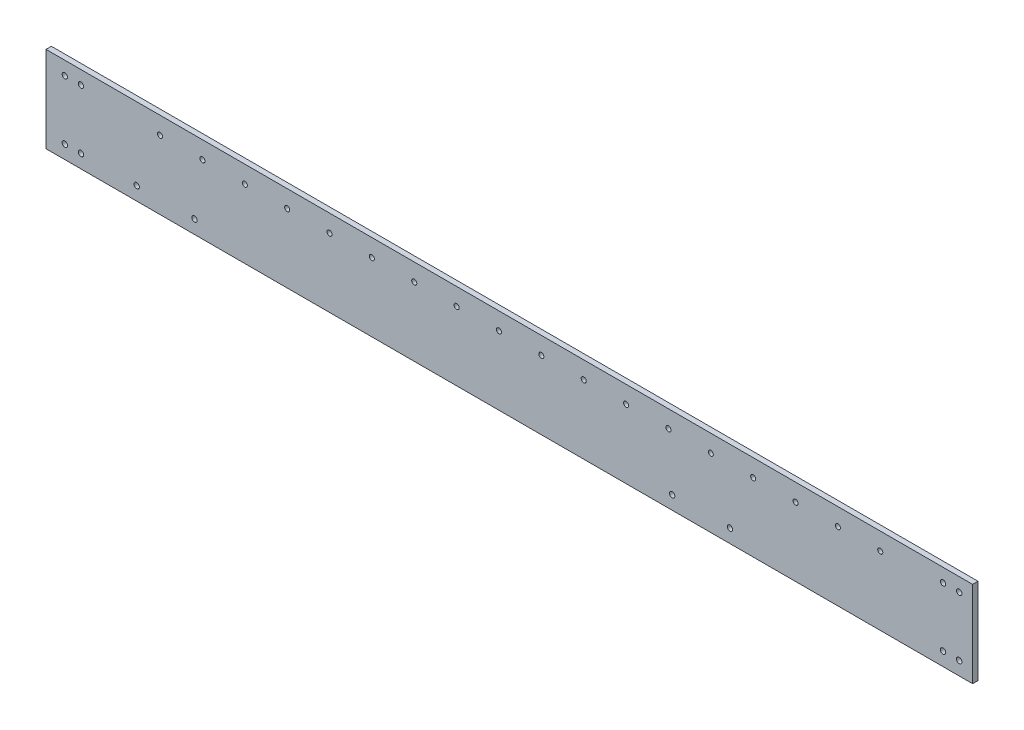
SolidWorks part; units mm, degrees
ref_plane "Front Plane" through (0, 0, 0) normal (0, 0, 1) x (1, 0, 0)
ref_plane "Top Plane" through (0, 0, 0) normal (0, 1, 0) x (1, 0, 0)
ref_plane "Right Plane" through (0, 0, 0) normal (1, 0, 0) x (0, 0, -1)
sketch "Sketch1" plane through (0, 0, 0) normal (1, 0, 0) x (0, 0, -1)
  line L0 (0, 0) -> (-3.175, 0)
  line L3 (-3.175, 0) -> (-3.175, 50.8)
  line L4 (-3.175, 50.8) -> (0, 50.8)
  line L5 (0, 50.8) -> (0, 0)
  dimension "LHeight" = 50.8
  dimension "LMaterialThickness" = 3.175
extrude "Boss-Extrude1" add sketch "Sketch1" along normal blind 546.825
sketch "LeftSideHoles-Sketch4" plane through (0, 0, 3.175) normal (0, 0, 1) x (1, 0, 0)
  line L0 (546.825, 50.8) -> (546.825, 0) construction
  line L1 (0, 50.8) -> (0, 0) construction
  line L2 (546.825, 50.8) -> (546.825, 0) construction
  line L3 (546.825, 50.8) -> (0, 50.8) construction
  line L4 (546.825, 0) -> (0, 0) construction
  line L5 (546.825, 50.8) -> (0, 50.8) construction
  line L6 (0, 50.8) -> (0, 0) construction
  circle A1 centre (11.1125, 42.8625) radius 1.5875
  circle A3 centre (529.3625, 42.8625) radius 1.5875
  circle A4 centre (20.6375, 42.8625) radius 1.5875
  circle A5 centre (538.8875, 42.8625) radius 1.5875
  circle A6 centre (11.1125, 7.9375) radius 1.5875
  circle A7 centre (20.6375, 7.9375) radius 1.5875
  circle A8 centre (529.3625, 7.9375) radius 1.5875
  circle A9 centre (538.8875, 7.9375) radius 1.5875
  circle A10 centre (492.325, 40.575) radius 1.5
  circle A11 centre (467.325, 40.575) radius 1.5
  circle A12 centre (442.325, 40.575) radius 1.5
  circle A13 centre (417.325, 40.575) radius 1.5
  circle A14 centre (392.325, 40.575) radius 1.5
  circle A15 centre (367.325, 40.575) radius 1.5
  circle A16 centre (342.325, 40.575) radius 1.5
  circle A17 centre (317.325, 40.575) radius 1.5
  circle A18 centre (292.325, 40.575) radius 1.5
  circle A19 centre (267.325, 40.575) radius 1.5
  circle A20 centre (242.325, 40.575) radius 1.5
  circle A21 centre (217.325, 40.575) radius 1.5
  circle A22 centre (192.325, 40.575) radius 1.5
  circle A23 centre (167.325, 40.575) radius 1.5
  circle A24 centre (142.325, 40.575) radius 1.5
  circle A25 centre (117.325, 40.575) radius 1.5
  circle A26 centre (92.325, 40.575) radius 1.5
  circle A27 centre (67.325, 40.575) radius 1.5
  circle A28 centre (53.5125, 7.9375) radius 1.5875
  circle A31 centre (369.5125, 7.9375) radius 1.5875
  circle A33 centre (87.6375, 7.9375) radius 1.5875
  circle A35 centre (403.6375, 7.9375) radius 1.5875
  dimension "D2" = 3.175
  dimension "D10" = 3
  dimension "D14" = 3.175
  dimension "D4" = 7.9375
  dimension "D1" = 11.1125
  dimension "D6" = 20.6375
  dimension "D3" = 7.9375
  dimension "D5" = 17.4625
  dimension "D7" = 7.9375
  dimension "D8" = 54.5
  dimension "D9" = 10.225
  dimension "D12" = 25
  dimension "D13" = 7.9375
  dimension "D15" = 53.5125
  dimension "D17" = 316
  dimension "D20" = 34.125
  dimension "D16" = 34.125
  dimension "D11" = 18
extrude "LeftSideHoles-Cut-Extrude3" cut sketch "LeftSideHoles-Sketch4" against normal through all
equation "\"RailThickness\"= .125in'Spec"
equation "\"SideRailHoleY1FromEdge\"= \"HoleOffsetFromEdge\""
equation "\"SideRailHoleX1FromSide\"= \"HoleOffsetFromSide\""
equation "\"MidSideRailLength\"= \"SideRailLength\" - \"RailThickness\"'Equals 546.825 => MidSideRail buts up against MidBackRail"
equation "\"VSWidth\"= 1.25in'Spec"
equation "\"HoleOffsetFromEdge\"= \"RailThickness\" * 2.5"
equation "\"HoleOffsetFromSide\"= \"RailThickness\" * 3.5"
equation "\"SideRailHoleX2FromSide\"= \"VSWidth\" - \"HoleOffsetFromEdge\" - \"RailThickness\"'Equals 20.6375"
equation "\"FasteningHoleDiameter\"= .125in"
equation "\"D2@LeftSideHoles-Sketch4\" = \"FasteningHoleDiameter\""
equation "\"LHeight@Sketch1\"=\"MidLeftOrRightSideRailHeight\""
equation "\"LMaterialThickness@Sketch1\"=\"RailThickness\""
equation "\"D1@Boss-Extrude1\"=\"MidSideRailLength\""
equation "\"D4@LeftSideHoles-Sketch4\" = \"SideRailHoleY1FromEdge\""
equation "\"D1@LeftSideHoles-Sketch4\"=\"SideRailHoleX1FromSide\""
equation "\"D6@LeftSideHoles-Sketch4\"=\"SideRailHoleX2FromSide\" "
equation "\"D3@LeftSideHoles-Sketch4\"=\"SideRailHoleX1FromSide\" - \"RailThickness\""
equation "\"D5@LeftSideHoles-Sketch4\"=\"SideRailHoleX2FromSide\" - \"RailThickness\""
equation "\"D7@LeftSideHoles-Sketch4\"=\"HoleOffsetFromEdge\""
equation "\"LinearRailXMountHole\"= \"StepperWidth\" + \"LinearRailFirstHoleOffsetFromEdge\""
equation "\"D8@LeftSideHoles-Sketch4\"=\"LinearRailXMountHole\""
equation "\"D9@LeftSideHoles-Sketch4\"=\"V6.3 GantryMiddleToToTopOfMidSideRail\""
equation "\"LinearRailHoleDistance\"= 25mm'Spec"
equation "\"D12@LeftSideHoles-Sketch4\"=\"LinearRailHoleDistance\""
equation "\"LinearRailFirstHoleOffsetFromEdge\"= 12.5mm'Spec"
equation "\"SideRailLength\"= 550mm"
equation "\"MidLeftOrRightSideRailHeight\"= 2.0in"
equation "\"StepperWidth\"= 42mm'Spec"
equation "\"StepperHolePadSize\"= \"StepperHoleDiameter\""
equation "\"MidRailRodStabilizerMountingHoleOffsetFromEdge\"= \"HoleOffsetFromEdge\""
equation "\"D13@LeftSideHoles-Sketch4\"=\"MidRailRodStabilizerMountingHoleOffsetFromEdge\""
equation "\"D14@LeftSideHoles-Sketch4\"=\"FasteningHoleDiameter\""
equation "\"DistanceFromBedFrontToFirstLeftStepperHole\"= \"LeadScrewNutPadSize\" + 10mm'Equals 34"
equation "\"BeltTensionerDepth\"= \"BeltTensionerBackWallThickness\" + \"BeltTensionerInnerDepth\"'Equals 23.4"
equation "\"20TGT2PulleyDiameter\"= 17.9mm'Spec"
equation "\"BeltTensionerSpaceBetweenPulleyAndWall\"= 1.5mm"
equation "\"BeltTensionerBackWallThickness\"= 4mm"
equation "\"BeltTensionerInnerDepth\"= \"20TGT2PulleyDiameter\" + \"BeltTensionerSpaceBetweenPulleyAndWall\""
equation "\"DistanceFromFrontSideToBedFront\"= \"RailThickness\" + \"BeltTensionerDepth\" + 10mm'Equals 36.575"
equation "\"DistanceFromFrontSideToFirstLeftStepperHole\"= \"DistanceFromFrontSideToBedFront\" + \"DistanceFromBedFrontToFirstLeftStepperHole\"'Equals 70.575"
equation "\"DistanceBetweenFrontToBackStepperHoles\"= \"BedLength\" - \"DistanceFromBedFrontToFirstLeftStepperHole\"'Equals 316"
equation "\"BedLength\"= \"BedInnerSquareLength\" + \"BedLWidth\" * 2 - \"BedOverlap\" * 2 + \"BedIncreasedByLength\"'Equals 350"
equation "\"BedOverlap\"= 20mm"
equation "\"BedThirdSize\"= 70mm"
equation "\"BedInnerSquareWidth\"= \"BedThirdSize\" * 3'Equals 210"
equation "\"BedLWidth\"= \"BedThirdSize\" + \"BedOverlap\"'Equals 90"
equation "\"BedIncreasedByLength\"= 0mm"
equation "\"LM8UUDiameter\"= 15mm"
equation "\"RodStabilizerDepth\"= \"LM8UUDiameter\" * 2"
equation "\"BedInnerSquareLength\"= \"BedInnerSquareWidth\""
equation "\"DistanceFromFrontSideToFirstLeftRodStabilizerMountingHole\"= \"DistanceFromFrontSideToFirstLeftStepperHole\" - \"DistanceFromStepperHoleToRodStabilizerMountingHole\"'Equals 53.5125"
equation "\"D15@LeftSideHoles-Sketch4\"=\"DistanceFromFrontSideToFirstLeftRodStabilizerMountingHole\""
equation "\"D17@LeftSideHoles-Sketch4\"=\"DistanceBetweenFrontToBackStepperHoles\""
equation "\"GABMidWallHeight\"= 28mm'Must equal 28 or changes alignment"
equation "\"20TGT2PulleyWidth\"= 8.7mm'The STL of the Pulley in the diagram is a bit larger"
equation "\"GABMidShortRiserHeight\"= \"GABMidWallHeight\" / 2 - \"20TGT2PulleyWidth\"'Equals 5.3"
equation "\"GABUpperHeight\"= 6mm"
equation "\"GABLowerHeight\"= 3mm"
equation "\"GABHeight\"= \"GABLowerHeight\" + \"GABMidWallHeight\" + \"GABUpperHeight\""
equation "\"GABRiserBossOffset\"= 0.8mm'Aligns Pulleys"
equation "\"StepperShaftLength\"= 24mm'Pulley will be attached to the end"
equation "\"V6.1 FromGantryPulleyToGantryMiddle\"= \"GABHeight\" / 2 - \"GABMidShortRiserHeight\" - \"GABLowerHeight\" + \"GABRiserBossOffset\" / 2"
equation "\"V6.2 GantryMiddleToTopOfMidBackRail\"= \"StepperShaftLength\" - \"V6.1 FromGantryPulleyToGantryMiddle\""
equation "\"V6.3 GantryMiddleToToTopOfMidSideRail\"= \"V6.2 GantryMiddleToTopOfMidBackRail\" - \"RailThickness\""
equation "\"LeadScrewNutMountingHoleFlangeDiameter\"= 22mm'Spec"
equation "\"LeadScrewNutPadSize\"= \"LeadScrewNutMountingHoleFlangeDiameter\" + 2mm'Equals 24"
equation "\"RodStabilizerMountingHoleOffsetInsideX\"= 14.125mm'Backward compatible"
equation "\"RodStabilizerMountingHoleOffsetOutsideX\"= 12mm"
equation "\"D20@LeftSideHoles-Sketch4\"=\"RodStabilizerLength\" - \"HoleOffsetFromEdge\" * 2"
equation "\"DistanceFromStepperHoleToRodStabilizerMountingHole\"= \"RodStabilizerLength\" / 2 - \"HoleOffsetFromEdge\"'Equals 17.0625"
equation "\"RodStabilizerLength\"= 50mm"
equation "\"D16@LeftSideHoles-Sketch4\"=\"RodStabilizerLength\" - \"HoleOffsetFromEdge\" * 2"
